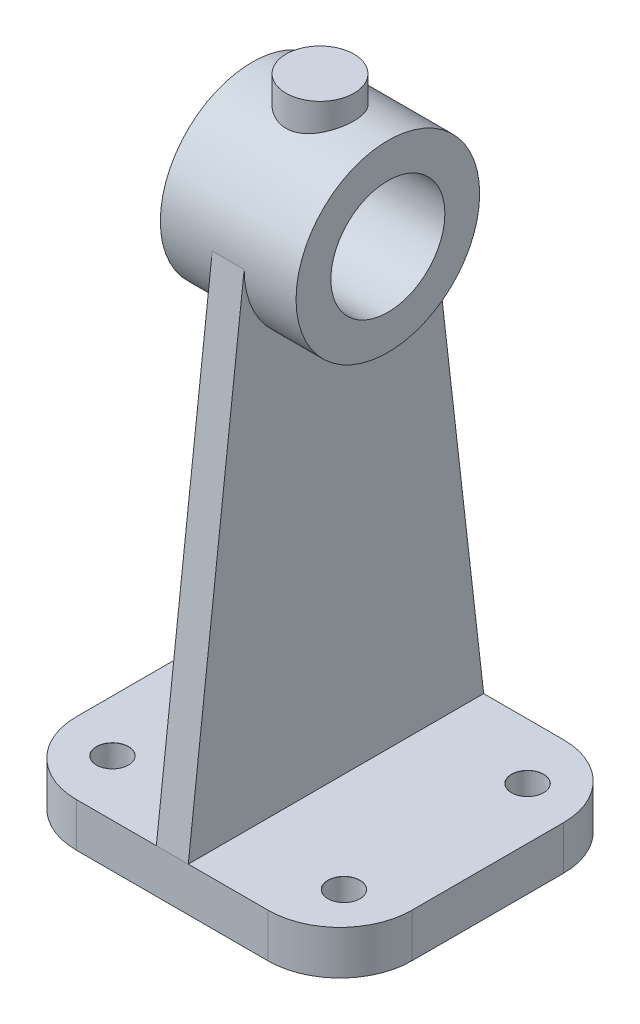
SolidWorks part; units mm, degrees
ref_plane "Front Plane" through (0, 0, 0) normal (0, 0, 1) x (1, 0, 0)
ref_plane "Top Plane" through (0, 0, 0) normal (0, 1, 0) x (1, 0, 0)
ref_plane "Right Plane" through (0, 0, 0) normal (1, 0, 0) x (0, 0, -1)
sketch "Sketch2" plane through (0, 0, 0) normal (0, 1, 0) x (1, 0, 0)
  line L1 (-42, -37) -> (42, -37)
  line L2 (-42, -37) -> (-42, 37)
  line L3 (-42, 37) -> (42, 37)
  line L4 (42, -37) -> (42, 37)
  line L5 (-42, -37) -> (42, 37) construction
  line L6 (-42, 37) -> (42, -37) construction
  point P0 (0, 0)
  dimension "D1" = 74
  dimension "D2" = 84
extrude "Boss-Extrude1" add sketch "Sketch2" along normal blind 11 contours L2 L3 L4 L1
fillet "Fillet1" radius 18 4 edges at (-42, 5.5, -37) (42, 5.5, -37) (42, 5.5, 37) (-42, 5.5, 37)
sketch "Sketch5" plane through (0, 11, 0) normal (0, 1, 0) x (1, 0, 0)
  point P0 (-29, 23)
  point P2 (29, 23)
  point P4 (29, -23)
  point P6 (-29, 23)
  point P7 (-29, -23)
  dimension "D1" = 46
  dimension "D2" = 58
  dimension "D3" = 29
  dimension "D4" = 23
hole_wizard "Ø8.0 (8) Diameter Hole1" positions "Sketch5" profile "Sketch4" hole size "Ø8.0" standard "ANSI Metric" end condition through all
sketch "Sketch4" plane through (-29, 11, -23) normal (1, 0, 0) x (0, 0, 1)
  line L0 (0, 0) -> (0, 11)
  line L1 (0, 11) -> (4, 11)
  line L2 (4, 11) -> (4, 0.025)
  line L3 (4, 0.025) -> (4.025, 0)
  line L5 (4.025, 0) -> (0, 0)
  line L6 (-4, 0.025) -> (-4.025, 0) construction
  line L11 (0, -6.35) -> (0, 107.95) construction
  dimension "Thru Hole Dia." = 8
  dimension "Thru Hole Depth" = 11
  dimension "Near C'Sink Dia." = 8.05
  dimension "Near C'Sink Angle" = 90
sketch "Sketch9" plane through (0, 0, 0) normal (1, 0, 0) x (0, 0, -1)
  line L0 (-37, 11) -> (-23, 133)
  line L1 (37, 11) -> (23, 133)
  line L2 (-37, 11) -> (37, 11)
  circle A0 centre (0, 133) radius 23
  dimension "D2" = 46
  dimension "D1" = 133
  dimension "D3" = 74
extrude "Boss-Extrude6" add sketch "Sketch9" along normal mid plane 8 contours A0 L0 L2 L1 region at (0, 60.0867, 0)
extrude "Boss-Extrude7" add sketch "Sketch9<9>" along normal mid plane 34 contours A0 region at (0, 133, 0)
sketch "Sketch9<9>" plane through (0, 0, 0) normal (1, 0, 0) x (0, 0, -1) same geometry as "Sketch9"
sketch "Sketch13" plane through (17, 0, 0) normal (1, 0, 0) x (0, 0, -1)
  point P0 (0, 133)
hole_wizard "Ø8.0 (28.57) Diameter Hole1" positions "Sketch13" profile "Sketch12" hole size "Ø8.0" standard "ANSI Metric" end condition through all
sketch "Sketch12" plane through (17, 133, 0) normal (0, 1, 0) x (0, 0, -1)
  line L0 (0, 0) -> (0, 59)
  line L1 (0, 59) -> (14.285, 59)
  line L2 (14.285, 59) -> (14.285, 0)
  line L5 (14.285, 0) -> (0, 0)
  line L11 (0, -6.35) -> (0, 107.95) construction
  dimension "Thru Hole Dia." = 28.57
  dimension "Thru Hole Depth" = 59
ref_plane "Plane2" through (0, 162, 0) normal (0, -1, 0) x (-1, 0, 0)
sketch "Sketch18" plane through (0, 162, 0) normal (0, -1, 0) x (-1, 0, 0)
  circle A0 centre (0, 0) radius 8.5
  dimension "D1" = 17
extrude "Boss-Extrude8" add sketch "Sketch18" along normal up to next
